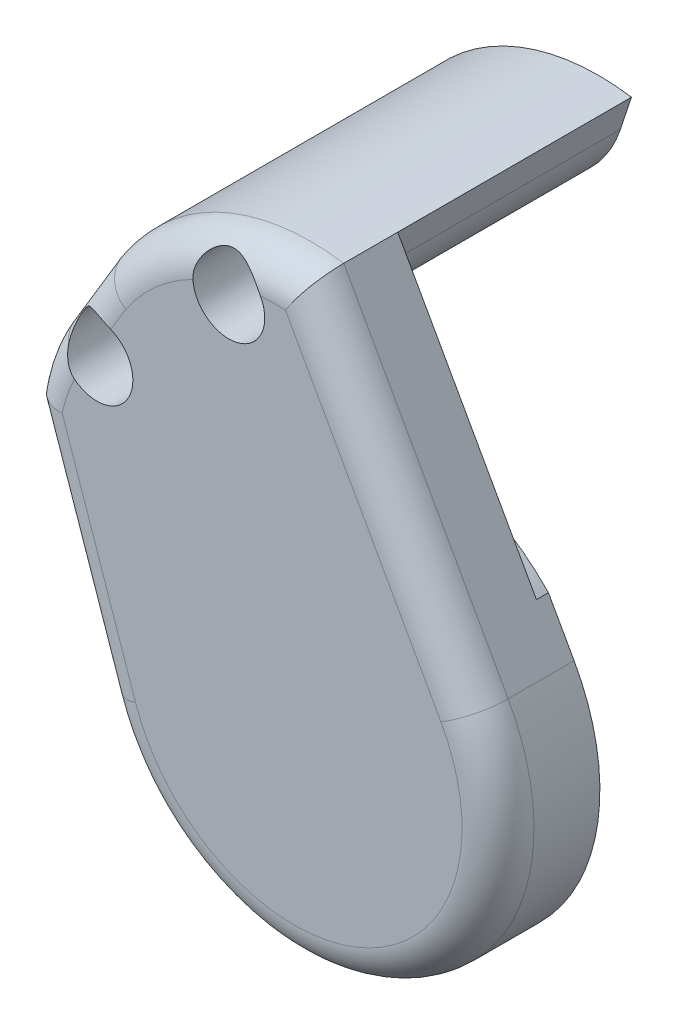
SolidWorks part; units mm, degrees
material "ABS"
ref_plane "Front Plane" through (0, 0, 0) normal (0, 0, 1) x (1, 0, 0)
ref_plane "Top Plane" through (0, 0, 0) normal (0, 1, 0) x (1, 0, 0)
ref_plane "Right Plane" through (0, 0, 0) normal (1, 0, 0) x (0, 0, -1)
sketch "Sketch1" plane through (0, 0, 0) normal (0, 0, 1) x (1, 0, 0)
  line L0 (-21.5118, -23.5649) -> (-14.5118, -23.5649)
  line L1 (0, -9.9671) -> (2.0631, -3.7458)
  line L3 (-15.6677, -11.5659) -> (-19.5301, -18.0027)
  arc A1 (-19.5301, -18.0027) -> (-21.5118, -23.5649) centre (-6.6677, -25.7195) ccw
  arc A2 (-15.6677, -11.5659) -> (2.0631, -3.7458) centre (-0.6677, -21.5651) cw
  arc A3 (-14.5118, -23.5649) -> (0, -9.9671) centre (21.0043, -46.9259) cw
  circle A4 centre (-4.5301, -8.0036) radius 1.8
  circle A5 centre (-15.5301, -18.0027) radius 1.8
  dimension "D1" = 7
  dimension "D8" = 3.6
  dimension "D2" = 2.0631
  dimension "D3" = 3.7458
  dimension "D4" = 16.9817
  dimension "D5" = 15.5614
  dimension "D6" = 5.9817
  dimension "D7" = 5.5622
extrude "Boss-Extrude1" add sketch "Sketch1" along normal blind 23
sketch "Sketch2" plane through (0, 0, 23) normal (0, 0, 1) x (1, 0, 0)
  line L0 (-15.6677, -11.5659) -> (-19.5301, -18.0027) construction
  line L1 (-15.6677, -11.5659) -> (-19.5301, -18.0027)
  line L2 (2.0631, -3.7458) -> (15.7796, -28.3476)
  line L3 (-21.5118, -23.5649) -> (-15.1513, -42.1348)
  arc A0 (-19.5301, -18.0027) -> (-21.5118, -23.5649) centre (-6.6677, -25.7195) ccw construction
  arc A1 (2.0631, -3.7458) -> (-15.6677, -11.5659) centre (-0.6677, -21.5651) ccw construction
  arc A2 (-19.5301, -18.0027) -> (-21.5118, -23.5649) centre (-6.6677, -25.7195) ccw
  arc A3 (2.0631, -3.7458) -> (-15.6677, -11.5659) centre (-0.6677, -21.5651) ccw
  arc A4 (15.7796, -28.3476) -> (-15.1513, -42.1348) centre (0.9315, -36.6261) cw
  circle A5 centre (-15.5301, -18.0027) radius 1.8 construction
  circle A6 centre (-4.5301, -8.0036) radius 1.8 construction
  circle A7 centre (-15.5301, -18.0027) radius 1.8
  circle A8 centre (-4.5301, -8.0036) radius 1.8
  dimension "D1" = 17
  dimension "D2" = 22.4433
  dimension "D3" = 13.0611
extrude "Boss-Extrude2" add sketch "Sketch2" along normal blind 4 and the other way blind 4.5
sketch "Sketch3" plane through (0, 0, 18.5) normal (0, 0, -1) x (-1, 0, 0)
  circle A0 centre (-0.9315, -36.6261) radius 11.25
  dimension "D1" = 22.5
  dimension "D2" = 32.8803
  dimension "D3" = 22.4433
extrude "Cut-Extrude1" cut sketch "Sketch3" against normal blind 7
sketch "Sketch4" plane through (0, 0, 18.5) normal (0, 0, -1) x (-1, 0, 0)
  circle A0 centre (-0.9315, -36.6261) radius 13
  dimension "D1" = 26
extrude "Cut-Extrude2" cut sketch "Sketch4" against normal blind 1.5
sketch "Sketch5" plane through (0, 0, 27) normal (0, 0, 1) x (1, 0, 0)
  circle A0 centre (-4.5301, -8.0036) radius 3
  circle A1 centre (-15.5301, -18.0027) radius 3
  dimension "D1" = 6
extrude "Cut-Extrude3" cut sketch "Sketch5" against normal blind 12
fillet "Fillet1" radius 3 6 edges at (-20.7974, -20.6853, 27) (8.9213, -16.0467, 27) (7.8526, -52.1534, 27) (-17.5989, -14.7843, 27) (-7.9425, -5.0708, 27) (-18.3315, -32.8499, 27)
sketch "Sketch6" plane through (0, 0, 18.5) normal (0, 0, -1) x (-1, 0, 0)
  line L0 (-2.0631, -3.7458) -> (0, -9.9671)
  line L1 (-2.0631, -3.7458) -> (-13.6368, -24.5042)
  line L2 (-15.7796, -28.3476) -> (-2.0631, -3.7458) construction
  line L3 (10.6831, -18.5879) -> (8.6095, -21.8839)
  arc A0 (-13.6368, -24.5042) -> (8.6095, -21.8839) centre (-0.9315, -36.6261) cw
  arc A1 (0, -9.9671) -> (10.6831, -18.5879) centre (-21.0043, -46.9259) cw
  arc A2 (14.5118, -23.5649) -> (0, -9.9671) centre (-21.0043, -46.9259) ccw construction
  dimension "D1" = 42.5104
  dimension "D2" = 17.5603
  dimension "D3" = 3.2959
  dimension "D4" = 10.6831
  dimension "D5" = 2.0736
  dimension "D6" = 11.5737
extrude "Cut-Extrude4" cut sketch "Sketch6" against normal blind 1
fillet "Fillet2" radius 10 2 edges at (-14.5118, -23.5649, 9.25) (0, -9.9671, 9.75)
